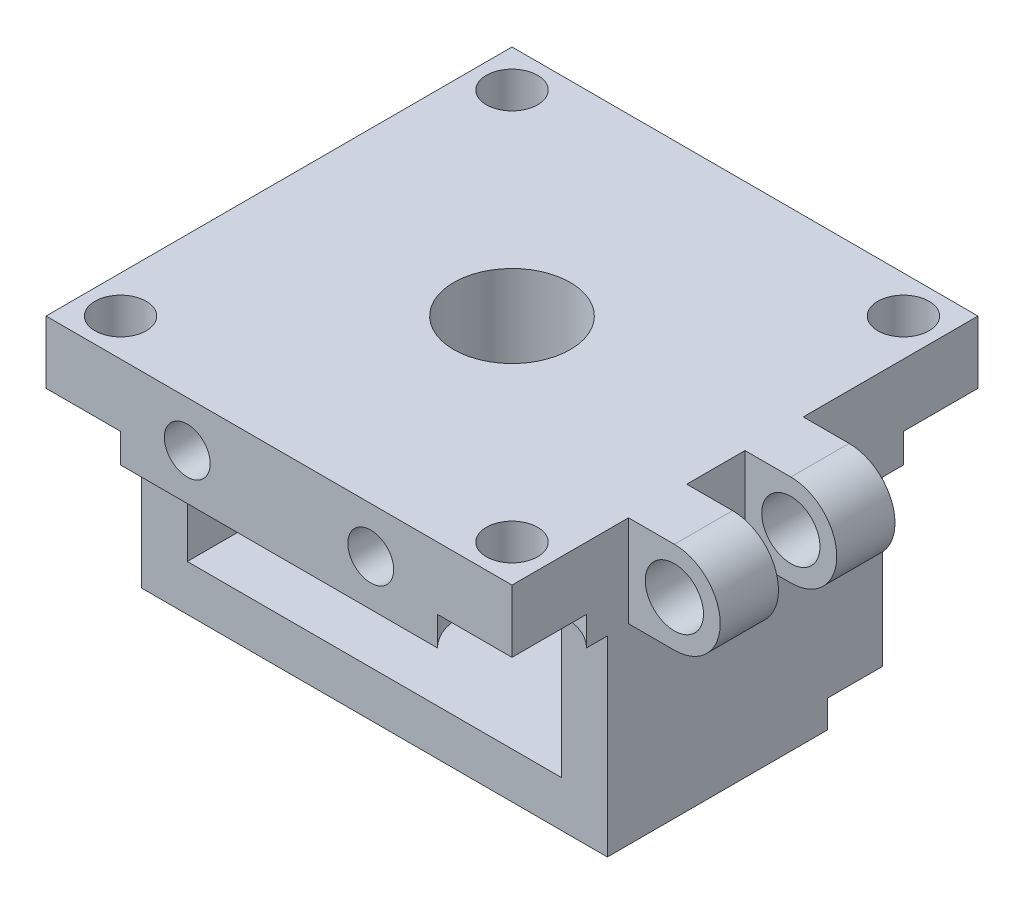
SolidWorks part; units mm, degrees
ref_plane "Front Plane" through (0, 0, 0) normal (0, 0, 1) x (1, 0, 0)
ref_plane "Top Plane" through (0, 0, 0) normal (0, 1, 0) x (1, 0, 0)
ref_plane "Right Plane" through (0, 0, 0) normal (1, 0, 0) x (0, 0, -1)
sketch "Sketch1" plane through (0, 0, 0) normal (0, 1, 0) x (1, 0, 0)
  line L1 (-25.4, -25.4) -> (25.4, -25.4)
  line L2 (-25.4, -25.4) -> (-25.4, 25.4)
  line L3 (-25.4, 25.4) -> (25.4, 25.4)
  line L4 (25.4, -25.4) -> (25.4, 25.4)
  line L5 (-25.4, -25.4) -> (25.4, 25.4) construction
  line L6 (-25.4, 25.4) -> (25.4, -25.4) construction
  circle A0 centre (-21.336, -21.336) radius 2.794
  circle A1 centre (21.336, -21.336) radius 2.794
  circle A2 centre (21.336, 21.336) radius 2.794
  circle A3 centre (-21.336, 21.336) radius 2.794
  circle A4 centre (0, 0) radius 6.35
  point P0 (0, 0)
  dimension "D3" = 5.588
  dimension "D4" = 12.7
  dimension "D1" = 50.8
  dimension "D2" = 21.336
extrude "Boss-Extrude1" add sketch "Sketch1" along normal blind 10
sketch "Sketch2" plane through (0, 0, 0) normal (0, -1, 0) x (1, 0, 0)
  circle A0 centre (-21.336, 21.336) radius 5.7474
  circle A1 centre (21.336, 21.336) radius 5.7474
  circle A2 centre (-21.336, -21.336) radius 5.7474
  circle A3 centre (21.336, -21.336) radius 5.7474
extrude "Cut-Extrude1" cut sketch "Sketch2" against normal mid plane 6.35
sketch "Sketch4" plane through (0, 0, 0) normal (0, 0, 1) x (1, 0, 0)
  line L0 (25.4, 10) -> (35.4, 10) construction
  line L1 (25.4, 0) -> (30.4, 0)
  line L2 (25.4, 0) -> (25.4, 10)
  line L3 (25.4, 10) -> (30.4, 10)
  arc A0 (30.4, 10) -> (30.4, 0) centre (30.4, 5) cw
  circle A1 centre (30.4, 5) radius 3.175
  point P12 (30.4, 10)
  dimension "D1" = 6.35
extrude "Boss-Extrude2" add sketch "Sketch4" along normal mid plane 25.4
sketch "Sketch5" plane through (0, 10, 0) normal (0, 1, 0) x (1, 0, 0)
  line L0 (35.4, -12.7) -> (35.4, 12.7) construction
  line L1 (25.4, 12.7) -> (35.4, 12.7)
  line L2 (25.4, 12.7) -> (25.4, 6.35)
  line L3 (25.4, 6.35) -> (35.4, 6.35)
  line L4 (35.4, 12.7) -> (35.4, 6.35)
  line L5 (25.4, 0) -> (25.4, -6.35)
  line L6 (25.4, 0) -> (35.4, 0)
  line L7 (35.4, 0) -> (35.4, -6.35)
  line L8 (25.4, -6.35) -> (35.4, -6.35)
  dimension "D1" = 6.35
  dimension "D3" = 6.35
  dimension "D2" = 2
extrude "Cut-Extrude2" cut sketch "Sketch5" against normal through all
sketch "Sketch10" plane through (0, 0, 0) normal (0, 0, 1) x (1, 0, 0)
  line L0 (25.4, 10) -> (25.4, 3.175) construction
  line L1 (-25.4, 0) -> (-20.4, 0)
  line L2 (-25.4, 0) -> (-25.4, -20.875)
  line L3 (-25.4, -20.875) -> (25.4, -20.875)
  line L4 (25.4, 0) -> (25.4, -20.875)
  line L6 (-20.4, 0) -> (-20.4, -15.875)
  line L7 (-20.4, -15.875) -> (20.4, -15.875)
  line L8 (20.4, 0) -> (20.4, -15.875)
  line L9 (20.4, 0) -> (25.4, 0)
  dimension "D1" = 5
  dimension "D2" = 5
  dimension "D3" = 5
  dimension "D4" = 15.875
extrude "Boss-Extrude6" add sketch "Sketch10" along normal mid plane 30
sketch "Sketch11" plane through (0, -20.875, 0) normal (0, -1, 0) x (1, 0, 0)
  line L0 (-25.4, -15) -> (25.4, -15) construction
  circle A0 centre (0, -12) radius 1.5
  dimension "D2" = 3
  dimension "D1" = 3
extrude "Cut-Extrude4" cut sketch "Sketch11" against normal up to surface (5 mm away) contours A0 up to face at (0, -15.875, 0)
sketch "Sketch12" plane through (0, -20.875, 0) normal (0, -1, 0) x (1, 0, 0)
  line L1 (25.4, -15) -> (-5, -15)
  line L2 (25.4, -15) -> (25.4, -9)
  line L3 (25.4, -9) -> (-5, -9)
  line L4 (-5, -15) -> (-5, -9)
  dimension "D1" = 6
  dimension "D2" = 5
extrude "Cut-Extrude5" cut sketch "Sketch12" against normal blind 3
sketch "Sketch13" plane through (0, -20.875, 0) normal (0, -1, 0) x (1, 0, 0)
  line L0 (7.5, -12) -> (-7.5, -12) construction
  line L1 (-25.4, -15) -> (-5, -15) construction
  circle A1 centre (-7.5, -12) radius 1.5
  circle A2 centre (0, -4.5) radius 1.5
  point P8 (0, -12)
  dimension "D1" = 3
  dimension "D4" = 3
  dimension "D2" = 3
  dimension "D3" = 15
  dimension "D5" = 7.5
extrude "Cut-Extrude6" cut sketch "Sketch13" against normal up to next
sketch "Sketch14" plane through (0, 0, 25.4) normal (0, 0, 1) x (1, 0, 0)
  line L0 (-10, 5) -> (10, 5) construction
  line L1 (-17.272, 0) -> (17.272, 0) construction
  circle A0 centre (-10, 5) radius 2.5
  circle A1 centre (10, 5) radius 2.5
  point P4 (7.8624, 4.5085)
  point P5 (0, 0)
  point P6 (0, 5)
  dimension "D1" = 5
  dimension "D2" = 20
  dimension "D3" = 5
extrude "Cut-Extrude7" cut sketch "Sketch14" against normal blind 20
